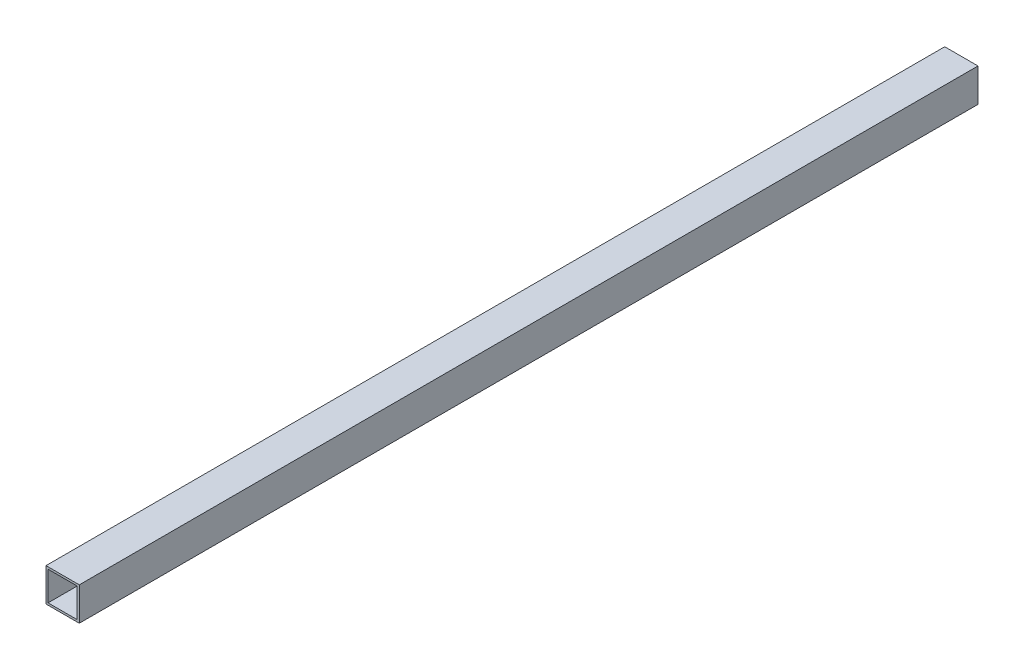
SolidWorks part; units mm, degrees
material "6061-T6 (SS)"
ref_plane "Front Plane" through (0, 0, 0) normal (0, 0, 1) x (1, 0, 0)
ref_plane "Top Plane" through (0, 0, 0) normal (0, 1, 0) x (1, 0, 0)
ref_plane "Right Plane" through (0, 0, 0) normal (1, 0, 0) x (0, 0, -1)
sketch "Sketch1" plane through (0, 0, 0) normal (0, 0, 1) x (1, 0, 0)
  line L1 (-12.7, -12.7) -> (12.7, -12.7)
  line L2 (-12.7, -12.7) -> (-12.7, 12.7)
  line L3 (-12.7, 12.7) -> (12.7, 12.7)
  line L4 (12.7, -12.7) -> (12.7, 12.7)
  line L5 (-12.7, -12.7) -> (12.7, 12.7) construction
  line L6 (-12.7, 12.7) -> (12.7, -12.7) construction
  point P0 (0, 0)
  dimension "D1" = 25.4
extrude "Boss-Extrude1" add sketch "Sketch1" along normal mid plane 685.8
shell "Shell1" thickness 1.5875 removed face at (0, 0, -342.9) removed face at (0, 0, 342.9)
